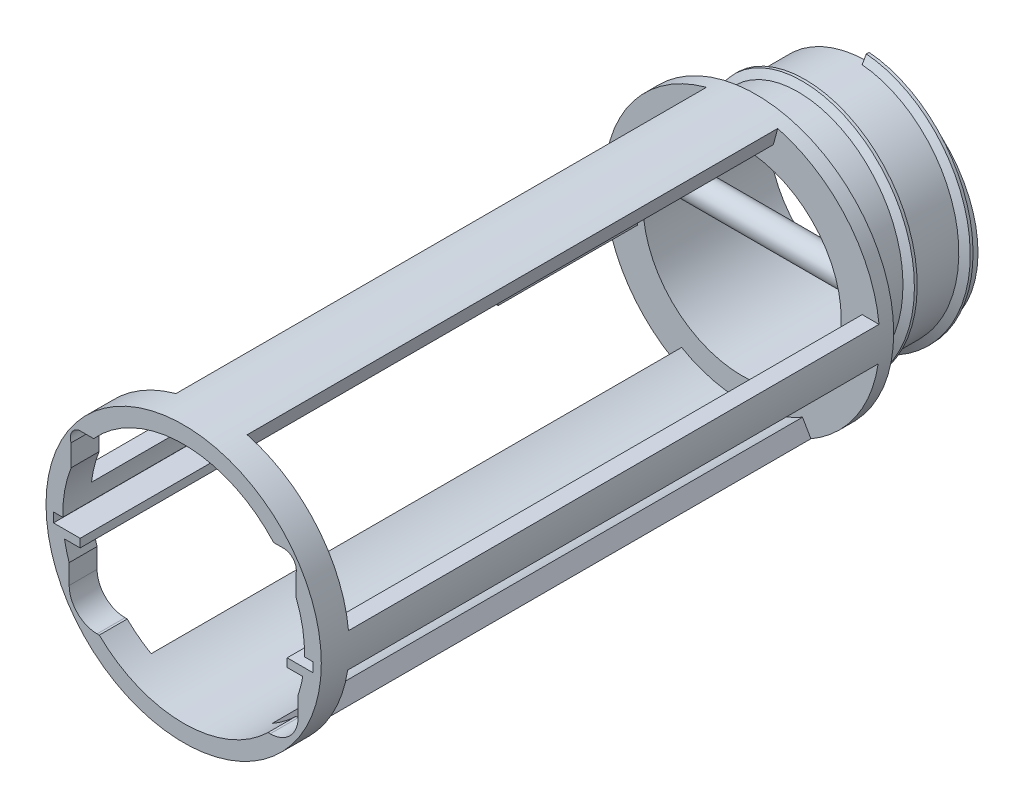
SolidWorks part; units mm, degrees
ref_plane "Front Plane" through (0, 0, 0) normal (0, 0, 1) x (1, 0, 0)
ref_plane "Top Plane" through (0, 0, 0) normal (0, 1, 0) x (1, 0, 0)
ref_plane "Right Plane" through (0, 0, 0) normal (1, 0, 0) x (0, 0, -1)
sketch "Sketch1" plane through (0, 0, 0) normal (0, 0, 1) x (1, 0, 0)
  circle A0 centre (0, 0) radius 19.75
  circle A1 centre (0, 0) radius 17.75
  dimension "D1" = 39.5
  dimension "D2" = 35.5
extrude "Boss-Extrude1" add sketch "Sketch1" along normal blind 20
sketch "Sketch2" plane through (0, 0, 20) normal (0, 0, 1) x (1, 0, 0)
  circle A2 centre (0, 0) radius 17.75 construction
  circle A3 centre (0, 0) radius 17.75
  circle A4 centre (0, 0) radius 24.65
extrude "Boss-Extrude2" add sketch "Sketch2" along normal blind 2.5 separate body
sketch "Sketch15" plane through (0, 0, 22.5) normal (0, 0, 1) x (1, 0, 0)
  circle A0 centre (0, 0) radius 21.65
  circle A1 centre (0, 0) radius 24.65 construction
  circle A2 centre (0, 0) radius 24.65
extrude "Boss-Extrude3" add sketch "Sketch15" along normal blind 100
sketch "Sketch16" plane through (0, 0, 122.5) normal (0, 0, 1) x (1, 0, 0)
  line L1 (-24.5229, -2.5) -> (-21.5052, -2.5)
  line L3 (-24.5229, 2.5) -> (-21.5052, 2.5)
  line L8 (21.5052, 2.5) -> (24.5229, 2.5)
  line L9 (21.5052, -2.5) -> (24.5229, -2.5)
  circle A0 centre (0, 0) radius 24.65 construction
  circle A1 centre (0, 0) radius 21.65 construction
  arc A2 (24.5229, 2.5) -> (-24.5229, 2.5) centre (0, 0) ccw
  arc A3 (21.5052, 2.5) -> (-21.5052, 2.5) centre (0, 0) ccw
  arc A4 (-21.5052, -2.5) -> (21.5052, -2.5) centre (0, 0) ccw
  arc A5 (-24.5229, -2.5) -> (24.5229, -2.5) centre (0, 0) ccw
  point P0 (0, 0)
extrude "Cut-Extrude2" cut sketch "Sketch16" against normal blind 95 from offset 5 offset against normal yes
sketch "Sketch18" plane through (0, 0, 122.5) normal (0, 0, 1) x (1, 0, 0)
  line L26 (-23.3071, -0.506) -> (23.1929, -0.506)
  line L27 (-23.3071, -0.506) -> (-23.3071, -2.206)
  line L28 (-23.3071, -2.206) -> (23.1929, -2.206)
  line L29 (23.1929, -0.506) -> (23.1929, -2.206)
  point P0 (-0.0571, -1.356)
  point P6 (0, 0)
  point P7 (0, 0)
sketch "Sketch19" plane through (0, 0, 122.5) normal (0, 0, 1) x (1, 0, 0)
  line L0 (-12.325, -21.3475) -> (-10.825, -18.7494)
  line L1 (12.325, -21.3475) -> (10.825, -18.7494)
  arc A0 (-12.325, -21.3475) -> (12.325, -21.3475) centre (0, 0) ccw
  circle A2 centre (0, 0) radius 21.65 construction
  arc A3 (-10.825, -18.7494) -> (10.825, -18.7494) centre (0, 0) ccw
extrude "Boss-Extrude5" add sketch "Sketch19" against normal blind 100
extrude "Cut-Extrude6" cut sketch "Sketch18" against normal blind 100
sketch "Sketch22" plane through (0, 0, 122.5) normal (0, 0, 1) x (1, 0, 0)
  line L0 (-21.5373, -2.206) -> (-18.5373, -2.206)
  line L1 (-18.5373, -2.206) -> (-18.5373, -3.706)
  line L2 (-18.5373, -3.706) -> (-21.3304, -3.706)
  line L4 (18.5373, -3.706) -> (21.3304, -3.706)
  line L5 (18.5373, -2.206) -> (18.5373, -3.706)
  line L6 (21.5373, -2.206) -> (18.5373, -2.206)
  arc A1 (-21.5373, -2.206) -> (21.5373, -2.206) centre (0, 0) ccw construction
  arc A2 (-21.5373, -2.206) -> (-21.3304, -3.706) centre (0, 0) ccw
  arc A3 (21.5373, -2.206) -> (21.3304, -3.706) centre (0, 0) cw
extrude "Boss-Extrude11" add sketch "Sketch22" against normal blind 25
sketch "Sketch23" plane through (0, 0, 122.5) normal (0, 0, 1) x (1, 0, 0)
  line L0 (-22.693, -2.206) -> (-18.693, -2.206)
  line L1 (-18.693, -2.206) -> (-18.693, -3.706)
  line L2 (-18.693, -3.706) -> (-22.4968, -3.706)
  line L3 (18.693, -3.706) -> (22.4968, -3.706)
  line L4 (18.693, -2.206) -> (18.693, -3.706)
  line L5 (22.693, -2.206) -> (18.693, -2.206)
  line L7 (18.5373, -2.206) -> (23.1929, -2.206) construction
  arc A0 (-22.693, -2.206) -> (-22.4968, -3.706) centre (0, 0) ccw
  arc A1 (22.693, -2.206) -> (22.4968, -3.706) centre (0, 0) cw
extrude "Boss-Extrude12" add sketch "Sketch23" along normal blind 25 from offset 100 offset against normal yes
sketch "Sketch26" plane through (0, 0, 122.5) normal (0, 0, 1) x (1, 0, 0)
  line L0 (22.4968, -3.706) -> (24.3698, -3.706)
  line L1 (24.3698, -3.706) -> (22.4968, -3.706)
  line L3 (-22.4968, -3.706) -> (-24.3698, -3.706)
  line L5 (18.693, -2.206) -> (23.1929, -2.206) construction
  line L6 (18.693, -2.206) -> (23.1929, -2.206)
  line L7 (23.1929, -2.206) -> (23.1929, -0.506) construction
  line L8 (23.1929, -2.206) -> (23.1929, -0.506)
  line L10 (-23.3071, -2.206) -> (-18.5373, -2.206) construction
  line L11 (23.1929, -0.506) -> (24.6448, -0.506)
  line L12 (-23.3071, -2.206) -> (-18.693, -2.206) construction
  line L13 (-23.3071, -2.206) -> (-22.693, -2.206)
  line L15 (-24.6448, -0.506) -> (-23.3071, -0.506)
  circle A0 centre (0, 0) radius 24.65 construction
  arc A1 (24.3698, -3.706) -> (24.6448, -0.506) centre (0, 0) ccw
  arc A3 (22.4968, -3.706) -> (22.693, -2.206) centre (0, 0) ccw
  arc A4 (-24.6448, -0.506) -> (-24.3698, -3.706) centre (0, 0) ccw
  arc A5 (22.4968, -3.706) -> (22.693, -2.206) centre (0, 0) ccw
  arc A6 (-22.4968, -3.706) -> (-22.693, -2.206) centre (0, 0) cw
  line M5 (23.1929, -2.206) -> (18.5373, -2.206)
  line M11 (-18.5373, -2.206) -> (-23.3071, -2.206)
  line M12 (-23.3071, -2.206) -> (-23.3071, -0.506)
  line M16 (23.1929, -0.506) -> (23.1929, -2.206)
  circle M17 centre (0, 0) radius 24.65
extrude "Boss-Extrude13" add sketch "Sketch26" against normal blind 100 contours L3 A6 L15 M11 M12 M17 | A3 L0 L11 M17 M16 M5 region at (23.7044, -2.2125, 122.5) region at (-23.722, -2.2457, 122.5)
sketch "Sketch27" plane through (0, 0, 0) normal (1, 0, 0) x (0, 0, -1)
  line L1 (-20, -24.65) -> (-20, 24.65) construction
  circle A0 centre (-15, 0) radius 2.3
  dimension "D1" = 5
sketch "Sketch32" plane through (0, 0, 122.5) normal (0, 0, 1) x (1, 0, 0)
  line L1 (-5.6034, 20.9123) -> (-6.3799, 23.8101)
  line L3 (5.6034, 20.9123) -> (6.3799, 23.8101)
  arc A0 (0, 21.65) -> (5.6034, 20.9123) centre (0, 0) cw
  arc A1 (21.6441, -0.506) -> (-21.6441, -0.506) centre (0, 0) ccw construction
  arc A2 (0, 21.65) -> (-5.6034, 20.9123) centre (0, 0) ccw
  circle A3 centre (0, 0) radius 24.65 construction
  arc A4 (6.3799, 23.8101) -> (-6.3799, 23.8101) centre (0, 0) ccw
sketch "Sketch33" plane through (0, 0, 122.5) normal (0, 0, 1) x (1, 0, 0)
  line L2 (-20.5, -10.506) -> (-20.5, -5.506)
  line L3 (15.5, -5.506) -> (-15.5, -5.506)
  line L5 (-15.5, -15.506) -> (15.5, -15.506)
  line L6 (-20.5, -5.506) -> (-15.5, -5.506)
  line L7 (20.5, -10.506) -> (20.5, -5.506)
  line L8 (20.5, -5.506) -> (15.5, -5.506)
  arc A0 (15.5, -15.506) -> (20.5, -10.506) centre (15.5, -10.506) ccw
  arc A5 (-20.5, -10.506) -> (-15.5, -15.506) centre (-15.5, -10.506) ccw
sketch "Sketch34" plane through (0, 0, 122.5) normal (0, 0, 1) x (1, 0, 0)
  line L3 (17.885, 14.4573) -> (-18.652, 14.4573)
  line L4 (-20.15, 11.794) -> (-20.15, 3.0878)
  line L5 (-20.15, 3.0878) -> (20.15, 3.0878)
  line L6 (20.15, 3.0878) -> (20.15, 11.794)
  arc A0 (17.885, 14.4573) -> (20.15, 11.794) centre (17.885, 12.1625) cw
  arc A1 (-18.652, 14.4573) -> (-20.15, 11.794) centre (-18.3358, 12.5266) ccw
  point P0 (0, 3.0878)
extrude "Cut-Extrude12" cut sketch "Sketch33" against normal blind 5
extrude "Cut-Extrude13" cut sketch "Sketch34" against normal blind 5
extrude "Boss-Extrude16" add sketch "Sketch32" against normal up to surface (100 mm away) up to face at (-0.0114, -3.9678, 22.5)
extrude "Boss-Extrude17" add sketch "Sketch27" along normal up to surface and the other way up to surface up to face at (17.75, 0, 20) other way up to face at (17.75, 0, 20)
sketch "Sketch35" plane through (0, 0, 0) normal (0, 0, -1) x (-1, 0, 0)
  circle A0 centre (0, 0) radius 19.75 construction
  circle A1 centre (0, 0) radius 19.75
curve "Helix/Spiral1" pitch 10 height 20 radius 19.75 left hand yes centre (0, 0, 0) axis (0, 0, 1) start towards (0, 1, 0)
sketch "Sketch36" plane through (0, 0, 0) normal (1, 0, 0) x (0, 0, -1)
  line L0 (-1, 19.75) -> (-0.25, 21.049)
  line L1 (-1, 19.75) -> (1, 19.75)
  line L2 (-0.25, 21.049) -> (0.25, 21.049)
  line L3 (0.25, 21.049) -> (1, 19.75)
  point P4 (0, 19.75)
  dimension "D1" = 60
  dimension "D2" = 60
  dimension "D3" = 2
  dimension "D4" = 0.5
sweep "Sweep1" add profiles "Sketch36" path "Helix/Spiral1"
